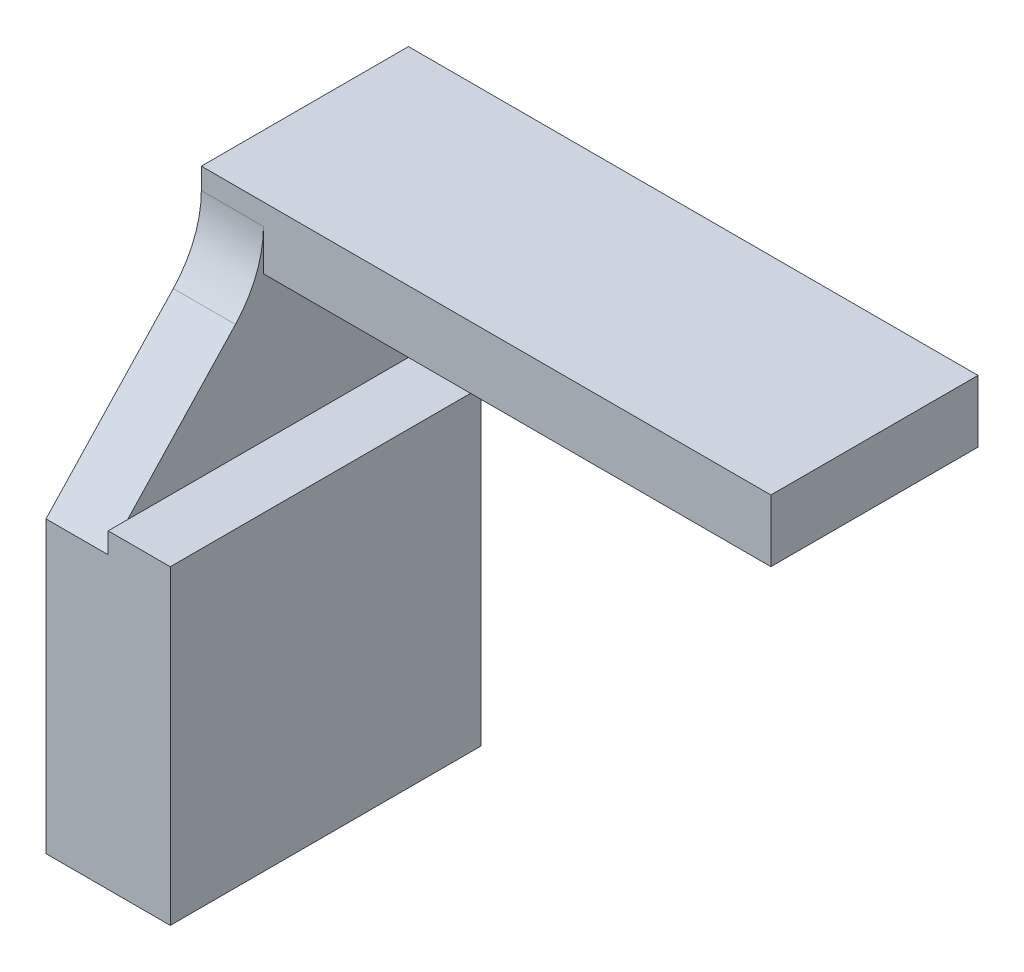
SolidWorks part; units mm, degrees
material "1060 Alloy"
ref_plane "Front Plane" through (0, 0, 0) normal (0, 0, 1) x (1, 0, 0)
ref_plane "Top Plane" through (0, 0, 0) normal (0, 1, 0) x (1, 0, 0)
ref_plane "Right Plane" through (0, 0, 0) normal (1, 0, 0) x (0, 0, -1)
sketch "Sketch1" plane through (0, 0, 0) normal (0, 1, 0) x (1, 0, 0)
  line L1 (-27.5, -10) -> (27.5, -10)
  line L2 (-27.5, -10) -> (-27.5, 10)
  line L3 (-27.5, 10) -> (27.5, 10)
  line L4 (27.5, -10) -> (27.5, 10)
  line L5 (-27.5, -10) -> (27.5, 10) construction
  line L6 (-27.5, 10) -> (27.5, -10) construction
  point P0 (0, 0)
  dimension "D1" = 20
  dimension "D2" = 55
extrude "Boss-Extrude1" add sketch "Sketch1" along normal blind 6
ref_plane "Plane1" through (-27.5, 0, 0) normal (-1, 0, 0) x (0, 0, 1)
sketch "Sketch2" plane through (-27.5, 0, 0) normal (-1, 0, 0) x (0, 0, 1)
  line L0 (10, 0) -> (-10, 0)
  line L1 (-10, 6) -> (-10, 0) construction
  line L2 (-5, -5) -> (-5, -44)
  line L4 (-5, -44) -> (25, -44)
  line L5 (25, -44) -> (25, -16)
  line L6 (25, -16) -> (10, 0)
  line L7 (-10, 0) -> (-5, -5)
  dimension "D1" = 39
  dimension "D2" = 5
  dimension "D3" = 30
  dimension "D4" = 28
  dimension "D5" = 5
extrude "Boss-Extrude2" add sketch "Sketch2" against normal blind 6
fillet "Fillet1" radius 10 1 edges
ref_plane "Plane2" through (-21.5, 0, 0) normal (1, 0, 0) x (0, 0, -1)
sketch "Sketch3" plane through (-21.5, 0, 0) normal (1, 0, 0) x (0, 0, -1)
  line L0 (-25, -44) -> (-25, -16) construction
  line L1 (5, -44) -> (-25, -44)
  line L2 (5, -44) -> (5, -14)
  line L3 (5, -14) -> (-25, -14)
  line L4 (-25, -44) -> (-25, -14)
  dimension "D1" = 30
extrude "Boss-Extrude3" add sketch "Sketch3" along normal blind 6
ref_point "gripper_finger_point"
